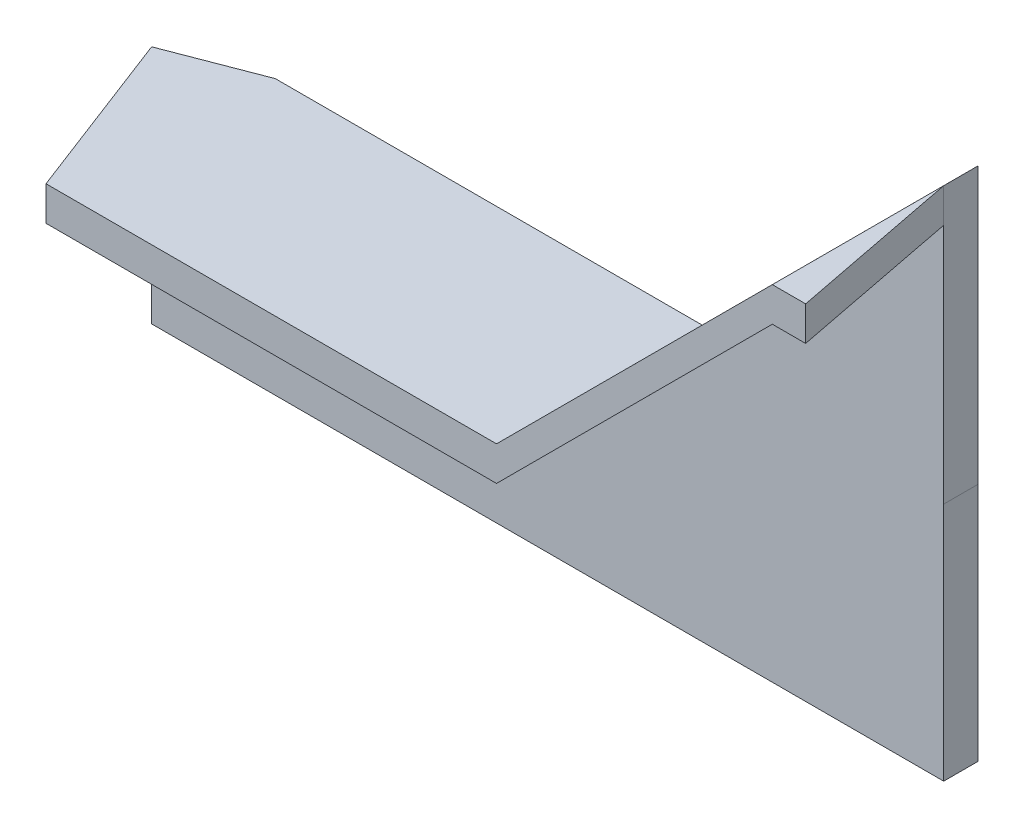
SolidWorks part; units mm, degrees
ref_plane "Płaszczyzna przednia" through (0, 0, 0) normal (0, 0, 1) x (1, 0, 0)
ref_plane "Płaszczyzna górna" through (0, 0, 0) normal (0, 1, 0) x (1, 0, 0)
ref_plane "Płaszczyzna prawa" through (0, 0, 0) normal (1, 0, 0) x (0, 0, -1)
sketch "Sketch1" plane through (0, 0, 0) normal (0, 0, 1) x (1, 0, 0)
  line L1 (-46.1789, 6.3455) -> (22.8211, 6.3455)
  line L2 (-46.1789, 6.3455) -> (-46.1789, -7.6545)
  line L3 (-46.1789, -7.6545) -> (22.8211, -7.6545)
  line L4 (22.8211, 6.3455) -> (22.8211, -7.6545)
  dimension "D1" = 14
  dimension "D2" = 69
extrude "Boss-Extrude1" add sketch "Sketch1" along normal blind 2
sketch "Sketch2" plane through (0, 0, 2) normal (0, 0, 1) x (1, 0, 0)
  line L1 (-46.1789, 6.3455) -> (6.7317, 6.3455)
  line L2 (-46.1789, 6.3455) -> (-46.1789, 4.3455)
  line L3 (-46.1789, 4.3455) -> (6.7317, 4.3455)
  line L4 (6.7317, 6.3455) -> (6.7317, 4.3455)
  point P7 (0, 0)
  point P8 (0, 0)
extrude "Boss-Extrude2" add sketch "Sketch2" along normal blind 4
sketch "Sketch4" plane through (0, 6.3455, 0) normal (0, 1, 0) x (1, 0, 0)
  line L0 (-18.1789, 0) -> (-33.8094, -6)
  line L4 (-33.8094, -6) -> (-46.1789, -6)
  line L5 (-46.1789, -6) -> (-46.1789, 0)
  line L6 (-46.1789, 0) -> (-18.1789, 0)
  dimension "D1" = 21
  dimension "D2" = 28
extrude "Cut-Extrude1" cut sketch "Sketch4" against normal blind 20 and the other way blind 20
sketch "Sketch5" plane through (0, 6.3455, 0) normal (0, 1, 0) x (1, 0, 0)
  line L1 (-33.8094, -6) -> (-18.1789, 0) construction
  line L7 (-33.8094, -6) -> (-23.3896, -2.0002)
  line L8 (-23.3896, -2.0002) -> (-21.8542, -6)
  line L9 (6.7317, -6) -> (-33.8094, -6) construction
  line L10 (-21.8542, -6) -> (-33.8094, -6)
  dimension "D1" = 90
extrude "Cut-Extrude2" cut sketch "Sketch5" against normal blind 2
sketch "Sketch6" plane through (0, 0, 2) normal (0, 0, 1) x (1, 0, 0)
  line L0 (6.7317, 6.3455) -> (22.8217, 22.4355)
  line L1 (22.8217, 22.4355) -> (22.8211, 6.3455)
  line L2 (22.8211, 6.3455) -> (6.7317, 6.3455)
  dimension "D1" = 45
  dimension "D2" = 16.0895
  dimension "D3" = 16.09
extrude "Boss-Extrude3" add sketch "Sketch6" against normal up to surface (2 mm away) up to face at (2.3211, -0.6545, 0)
sketch "Sketch7" plane through (0, 0, 2) normal (0, 0, 1) x (1, 0, 0)
  line L0 (6.7317, 4.3455) -> (22.8216, 20.4355)
  line L1 (22.8211, 6.3455) -> (22.8217, 22.4355) construction
  line L2 (22.8216, 20.4355) -> (22.8217, 22.4355)
  line L3 (22.8217, 22.4355) -> (6.7317, 6.3455)
  line L4 (6.7317, 6.3455) -> (6.7317, 4.3455)
  dimension "D1" = 2
extrude "Boss-Extrude4" add sketch "Sketch7" along normal up to surface (4 mm away) up to face at (-7.5613, 5.3455, 6)
sketch "Sketch8" plane through (0, 0, 6) normal (0, 0, 1) x (1, 0, 0)
  line L0 (22.8217, 22.4355) -> (6.7317, 6.3455)
  line L1 (6.7317, 6.3455) -> (-21.8542, 6.3455)
  line L2 (-21.8542, 6.3455) -> (-21.8542, 4.3455)
  line L3 (-21.8542, 4.3455) -> (6.7317, 4.3455)
  line L4 (6.7317, 4.3455) -> (22.8216, 20.4355)
  line L5 (22.8216, 20.4355) -> (22.8217, 22.4355)
extrude "Boss-Extrude5" add sketch "Sketch8" along normal blind 6
sketch "Sketch9" plane through (0, 4.3455, 0) normal (0, -1, 0) x (1, 0, 0)
  line L0 (-23.389, 2) -> (-21.8542, 6)
  line L1 (-21.8542, 6) -> (-19.552, 12)
  line L2 (-21.8542, 12) -> (6.7317, 12) construction
  line L3 (-19.552, 12) -> (-21.8542, 12)
  line L4 (-21.8542, 12) -> (-23.389, 2)
extrude "Cut-Extrude3" cut sketch "Sketch9" against normal blind 6
sketch "Sketch10" plane through (0, 4.3455, 0) normal (0, -1, 0) x (1, 0, 0)
  line L0 (22.8216, 12) -> (24.7654, 12)
  line L1 (24.7654, 12) -> (22.8211, 2)
  line L2 (22.8211, 2) -> (22.8216, 12)
  dimension "D1" = 11
extrude "Boss-Extrude6" add sketch "Sketch10" against normal blind 2 from vertex starting at point (22.8216, 20.4355, 2)
